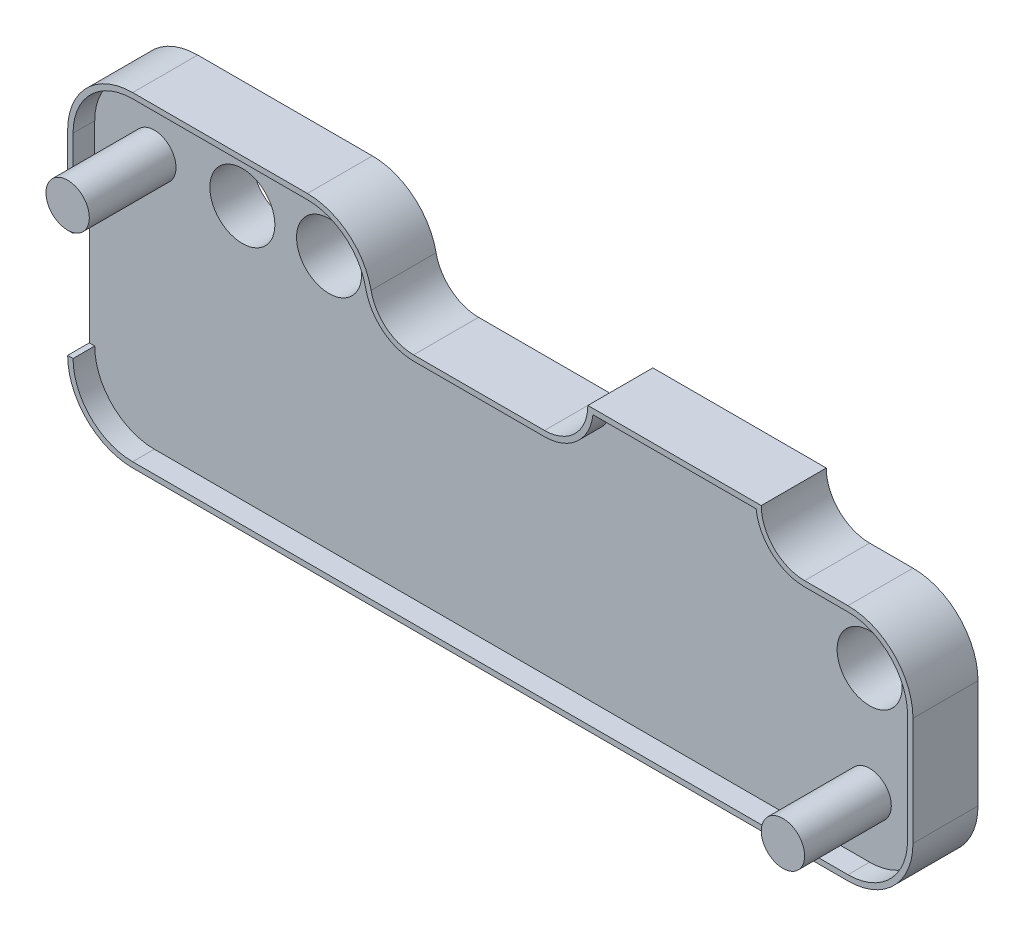
SolidWorks part; units mm, degrees
ref_plane "Front Plane" through (0, 0, 0) normal (0, 0, 1) x (1, 0, 0)
ref_plane "Top Plane" through (0, 0, 0) normal (0, 1, 0) x (1, 0, 0)
ref_plane "Right Plane" through (0, 0, 0) normal (1, 0, 0) x (0, 0, -1)
sketch "Sketch1" plane through (0, 0, 0) normal (0, 0, 1) x (1, 0, 0)
  line L0 (3, 0) -> (36, 0)
  line L1 (39, 3) -> (39, 8)
  line L2 (36, 11) -> (34, 11)
  line L4 (32, 13) -> (24, 13)
  line L6 (22, 11) -> (15.9596, 11)
  line L8 (11.0606, 15) -> (3, 15)
  line L9 (0, 12) -> (0, 3)
  line L10 (3, 0.25) -> (36, 0.25)
  line L11 (38.75, 3) -> (38.75, 8)
  line L12 (36, 10.75) -> (34, 10.75)
  line L13 (31.7639, 12.75) -> (24.2361, 12.75)
  line L14 (22, 10.75) -> (15.9596, 10.75)
  line L15 (11.0606, 14.75) -> (3, 14.75)
  line L16 (0.25, 12) -> (0.25, 3)
  arc A0 (14, 12.6) -> (11.0606, 15) centre (11.0606, 12) ccw
  arc A1 (36, 0) -> (39, 3) centre (36, 3) ccw
  arc A2 (39, 8) -> (36, 11) centre (36, 8) ccw
  arc A3 (3, 15) -> (0, 12) centre (3, 12) ccw
  arc A4 (3, 0) -> (0, 3) centre (3, 3) cw
  arc A5 (14, 12.6) -> (15.9596, 11) centre (15.9596, 13) ccw
  arc A6 (24, 13) -> (22, 11) centre (22, 13) cw
  arc A7 (32, 13) -> (34, 11) centre (34, 13) ccw
  circle A8 centre (11.0606, 12) radius 1.5
  circle A10 centre (7.0606, 12) radius 1.5
  circle A12 centre (3, 12) radius 1
  circle A13 centre (36, 8) radius 1.5
  circle A14 centre (36, 3) radius 1
  arc A15 (36, 0.25) -> (38.75, 3) centre (36, 3) ccw
  arc A16 (38.75, 8) -> (36, 10.75) centre (36, 8) ccw
  arc A17 (31.7639, 12.75) -> (34, 10.75) centre (34, 13) ccw
  arc A18 (24.2361, 12.75) -> (22, 10.75) centre (22, 13) cw
  arc A19 (13.7551, 12.55) -> (15.9596, 10.75) centre (15.9596, 13) ccw
  arc A20 (13.7551, 12.55) -> (11.0606, 14.75) centre (11.0606, 12) ccw
  arc A21 (3, 14.75) -> (0.25, 12) centre (3, 12) ccw
  arc A22 (3, 0.25) -> (0.25, 3) centre (3, 3) cw
  point P21 (0, 0)
  dimension "D1" = 3
  dimension "D9" = 2
  dimension "D10" = 2
  dimension "D11" = 2
  dimension "D12" = 3
  dimension "D13" = 2
  dimension "D14" = 3
  dimension "D16" = 3
  dimension "D17" = 2
  dimension "D2" = 15
  dimension "D3" = 11
  dimension "D4" = 2
  dimension "D5" = 7
  dimension "D6" = 10
  dimension "D7" = 14
  dimension "D8" = 39
  dimension "D15" = 4
  dimension "D18" = 0.25
extrude "Boss-Extrude1" add sketch "Sketch1" along normal blind 2 contours A22 L10 A15 L11 A16 L12 A17 L13 A18 L14 A19 A20 L15 A21 L16 A14 A13 A12 A10 A8 region at (18.3798, 6.3209, 0)
extrude "Boss-Extrude2" add sketch "Sketch1<3>" along normal blind 3 contours L0 A1 L1 A2 L2 A7 L4 A6 L6 A5 A0 L8 A3 L9 A4 | L10 A15 L11 A16 L12 A17 L13 A18 L14 A19 A20 L15 A21 L16 A22
sketch "Sketch1<3>" plane through (0, 0, 0) normal (0, 0, 1) x (1, 0, 0) same geometry as "Sketch1"
extrude "Boss-Extrude3" add sketch "Sketch1<4>" along normal blind 6 contours A12 | A14 region at (3, 12, 0) region at (36, 3, 0)
sketch "Sketch1<4>" plane through (0, 0, 0) normal (0, 0, 1) x (1, 0, 0) same geometry as "Sketch1"
sketch "Sketch2" plane through (0, 0, 0) normal (-1, 0, 0) x (0, 0, 1)
  line L0 (2, 12) -> (2, 3) construction
  line L1 (2, 8) -> (6, 8)
  line L2 (2, 8) -> (2, 3)
  line L3 (2, 3) -> (6, 3)
  line L4 (6, 8) -> (6, 3)
  line L5 (3, 0) -> (0, 0) construction
  line L6 (6, 11) -> (6, 13) construction
  line L7 (6, 11) -> (6, 0) construction
  line L8 (2, 11) -> (6, 11) construction
  point P6 (6, 5.5)
  point P7 (0, 0)
  point P14 (0, 0)
  point P15 (0, 0)
  point P18 (0, 0)
  point P19 (6, 5.5)
  dimension "D1" = 5
extrude "Cut-Extrude1" cut sketch "Sketch2" against normal mid plane 6
